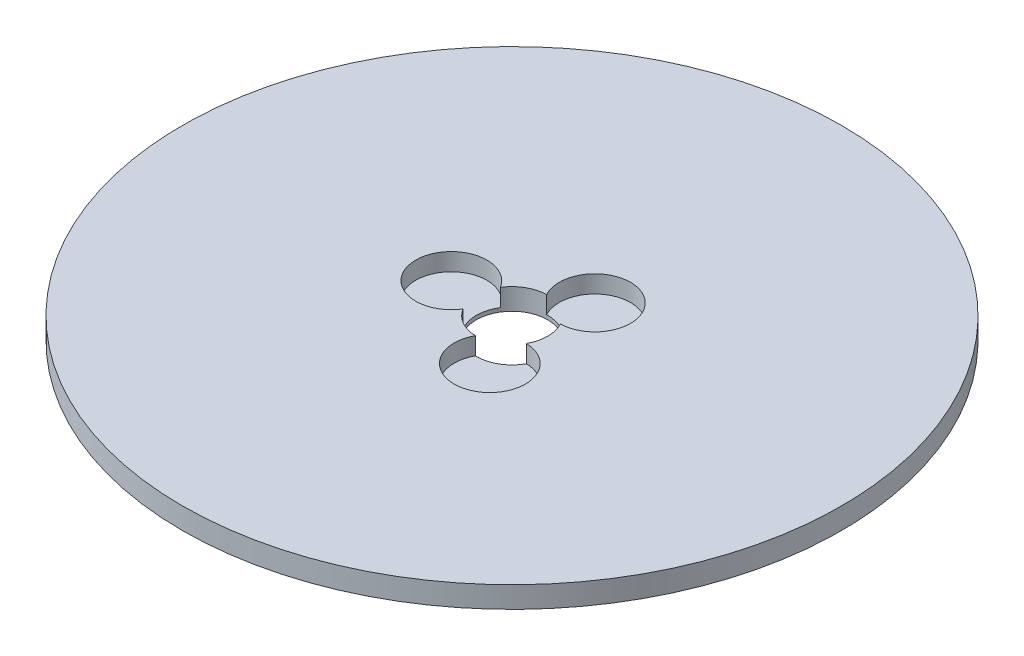
SolidWorks part; units mm, degrees
ref_plane "Front Plane" through (0, 0, 0) normal (0, 0, 1) x (1, 0, 0)
ref_plane "Top Plane" through (0, 0, 0) normal (0, 1, 0) x (1, 0, 0)
ref_plane "Right Plane" through (0, 0, 0) normal (1, 0, 0) x (0, 0, -1)
sketch "Sketch1" plane through (0, 0, 0) normal (0, 1, 0) x (1, 0, 0)
  circle A0 centre (0, 0) radius 92.5
  dimension "FLANGE_OD" = 185
extrude "Boss-Extrude1" add sketch "Sketch1" along normal blind 6
sketch "Sketch2" plane through (0, 0, 0) normal (0, 1, 0) x (1, 0, 0)
  circle A0 centre (0, 0) radius 10
  dimension "BORE_D" = 20
extrude "Cut-Extrude1" cut sketch "Sketch2" along normal through all
sketch "Sketch3" plane through (0, 6, 0) normal (0, 1, 0) x (1, 0, 0)
  circle A0 centre (0, 0) radius 17.0297 construction
  circle A1 centre (-17.0297, 0) radius 10
  dimension "BOLT_D" = 20
  dimension "BOLT_PCD" = 34.0593
extrude "Cut-Extrude2" cut sketch "Sketch3" against normal blind 4.9149
pattern_circular "CirPattern1" count 3 over 360 about axis through (0, 0, 0) along (0, 1, 0) of "Cut-Extrude2"
